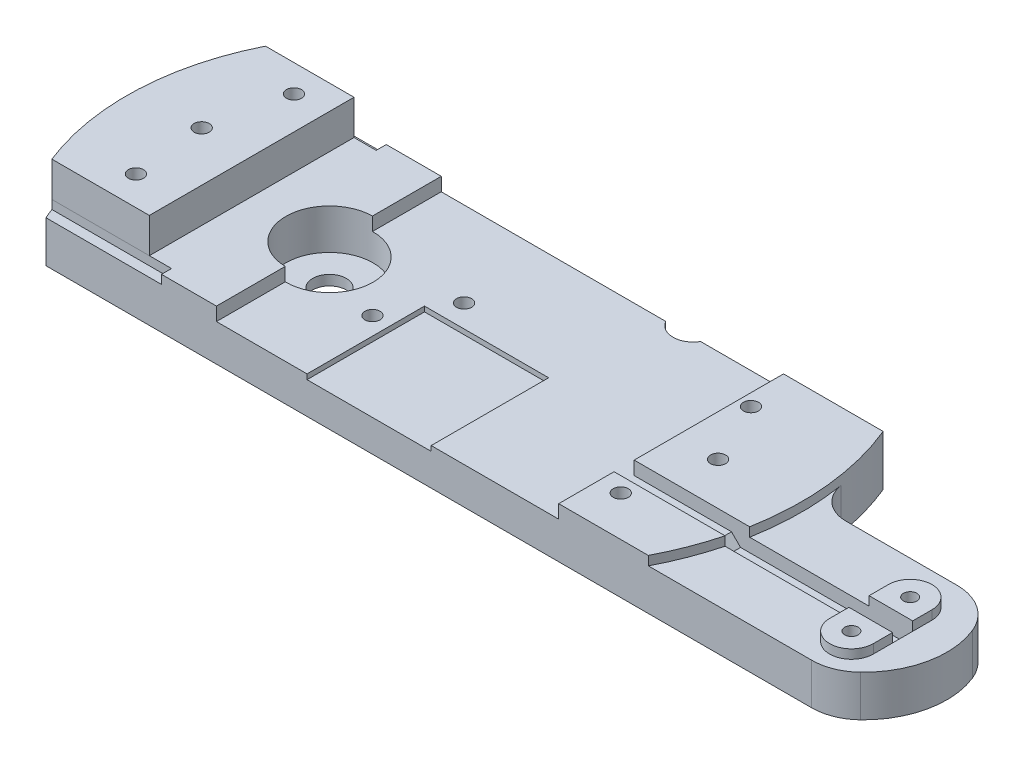
SolidWorks part; units mm, degrees
material "1060 Alloy"
ref_plane "Front Plane" through (0, 0, 0) normal (0, 0, 1) x (1, 0, 0)
ref_plane "Top Plane" through (0, 0, 0) normal (0, 1, 0) x (1, 0, 0)
ref_plane "Right Plane" through (0, 0, 0) normal (1, 0, 0) x (0, 0, -1)
sketch "Sketch1" plane through (0, 0, 0) normal (0, 1, 0) x (1, 0, 0)
  line L1 (-97.5, -33.5) -> (97.5, -33.5)
  line L2 (-97.5, -33.5) -> (-97.5, 33.5)
  line L3 (-97.5, 33.5) -> (97.5, 33.5)
  line L4 (97.5, -33.5) -> (97.5, 33.5)
  line L5 (-97.5, -33.5) -> (97.5, 33.5) construction
  line L6 (-97.5, 33.5) -> (97.5, -33.5) construction
  point P0 (0, 0)
  dimension "D1" = 67
  dimension "D2" = 195
extrude "Boss-Extrude1" add sketch "Sketch1" along normal blind 25.4
sketch "Sketch2" plane through (0, 0, 0) normal (0, -1, 0) x (1, 0, 0)
  line L0 (-97.5, -33.5) -> (-97.5, 33.5) construction
  line L1 (97.5, 33.5) -> (97.5, -33.5) construction
  line L2 (97.5, 33.5) -> (88.5, 33.5)
  line L3 (-97.5, 33.5) -> (97.5, 33.5) construction
  line L4 (97.5, -33.5) -> (91.5, -33.5)
  line L5 (97.5, -33.5) -> (-97.5, -33.5) construction
  line L6 (-97.5, 33.5) -> (-91, 33.5)
  line L7 (-97.5, -33.5) -> (-88, -33.5)
  circle A0 centre (18.0922, -3.2198) radius 79.4078
  circle A1 centre (-22.6589, 2.9929) radius 74.8411
  line M7 (97.5, -33.5) -> (97.5, 33.5)
  line M8 (97.5, 33.5) -> (-97.5, 33.5)
  line M9 (-97.5, 33.5) -> (-97.5, -33.5)
  line M10 (-97.5, -33.5) -> (97.5, -33.5)
  dimension "D1" = 9
  dimension "D2" = 6
  dimension "D3" = 6.5
  dimension "D4" = 9.5
extrude "Cut-Extrude1" cut sketch "Sketch2" against normal through all contours A0 M7 M8 | A0 M10 M7 | A1 M9 M10 | A1 M8 M9 region at (94.8284, 0, 24.4273) region at (95.7123, 0, -25.9883) region at (-95.5654, 0, 25.941) region at (-94.6839, 0, -24.4966)
sketch "Sketch3" plane through (0, 0, 33.5) normal (0, 0, -1) x (-1, 0, 0)
  line L0 (97.5, 25.4) -> (63.2, 25.4)
  line L2 (63.2, 25.4) -> (63.2, 15)
  line L3 (63.2, 15) -> (40.2, 15)
  line L4 (40.2, 15) -> (40.2, 11)
  line L5 (40.2, 11) -> (-61.8, 11)
  line L6 (-91.5, 25.4) -> (88, 25.4) construction
  line L10 (97.5, 0) -> (97.5, 25.4) construction
  line L11 (-61.8, 11) -> (-61.8, 15)
  line L12 (-61.8, 15) -> (-97.5, 15)
  line L13 (-97.5, 25.4) -> (-97.5, 0) construction
  line L14 (-97.5, 15) -> (-97.5, 25.4)
  line L15 (-97.5, 25.4) -> (63.2, 25.4)
  line M13 (-88.5, 0) -> (-88.5, 25.4)
  line M14 (-88.5, 25.4) -> (91, 25.4)
  dimension "D1" = 10.4
  dimension "D2" = 34.3
  dimension "D3" = 23
  dimension "D4" = 4
  dimension "D5" = 102
extrude "Cut-Extrude2" cut sketch "Sketch3" along normal through all contours L11 L12 L2 L3 L4 L5 M13 M14 | L2 L3 L4 L5 L11 L12 L14 L15 region at (12.2699, 18.7206, 33.5)
sketch "Sketch4" plane through (0, 25.4, 0) normal (0, 1, 0) x (1, 0, 0)
  line L0 (-56.5873, 33.5) -> (-56.5873, 30.5)
  line L1 (-63.2, 33.5) -> (-88, 33.5) construction
  line L2 (-56.5873, 30.5) -> (-89.5873, 30.5)
  line L3 (-56.5873, -33.5) -> (-56.5873, -30.5)
  line L4 (-91, -33.5) -> (-63.2, -33.5) construction
  line L5 (-56.5873, -30.5) -> (-92.2617, -30.5)
  line L6 (-56.5873, 33.5) -> (-63.2, 33.5)
  line L7 (-56.5873, -33.5) -> (-63.2, -33.5)
  arc A0 (-88, 33.5) -> (-91, -33.5) centre (-22.6589, -2.9929) ccw construction
  line M5 (-91, -33.5) -> (-63.2, -33.5)
  line M6 (-63.2, -33.5) -> (-63.2, 33.5)
  line M7 (-63.2, 33.5) -> (-88, 33.5)
  arc M8 (-88, 33.5) -> (-91, -33.5) centre (-22.6589, -2.9929) ccw
  dimension "D1" = 3
  dimension "D2" = 3
  dimension "D3" = 33
extrude "Cut-Extrude3" cut sketch "Sketch4" against normal blind 13 contours L2 M6 M7 M8 | L0 L6 L2 M6 | L5 M6 M8 M5 | L7 L3 L5 M6 region at (-59.8937, 25.4, -32) region at (-76.0082, 25.4, -31.9845) region at (-77.4242, 25.4, 31.9889) region at (-59.8937, 25.4, 32)
sketch "Sketch6" plane through (0, 0, 0) normal (0, -1, 0) x (1, 0, 0)
  line L0 (-63.2, -33.5) -> (-97.5, -33.5)
  line L1 (91.5, -33.5) -> (-88, -33.5) construction
  line L2 (-63.2, -33.5) -> (-63.2, 33.5)
  line L3 (-91, 33.5) -> (88.5, 33.5) construction
  line L4 (-63.2, -9) -> (-28.1, -9) construction
  line L5 (-63.2, 8.7) -> (-18.5, 8.7) construction
  line L6 (-63.2, -8.2) -> (-8.1, -8.2) construction
  line L8 (91.5, -33.5) -> (-88, -33.5) construction
  line L9 (-97.5, -33.5) -> (-97.5, 33.5)
  line L10 (-97.5, 33.5) -> (-63.2, 33.5)
  circle A1 centre (-18.5, 8.7) radius 2.25
  circle A2 centre (74.1, -1.7) radius 2.25
  circle A3 centre (68.3, 21.5) radius 2.25
  circle A4 centre (65.4, -20.2) radius 2.25
  circle A5 centre (-8.1, -8.2) radius 2.25
  circle A6 centre (-75.9, 21.8) radius 2.25
  circle A7 centre (-78, 0.1) radius 2.25
  circle A8 centre (-73, -22.4) radius 2.25
  arc A10 (-91, 33.5) -> (-88, -33.5) centre (-22.6589, 2.9929) ccw construction
  dimension "D22" = 4.5
  dimension "D3" = 35.1
  dimension "D4" = 34.3
  dimension "D5" = 44.7
  dimension "D6" = 24.5
  dimension "D7" = 55.1
  dimension "D8" = 42.2
  dimension "D9" = 137.3
  dimension "D10" = 128.6
  dimension "D11" = 131.5
  dimension "D12" = 9.8
  dimension "D13" = 14.8
  dimension "D14" = 12.7
  dimension "D15" = 11.1
  dimension "D16" = 33.6
  dimension "D17" = 55.3
  dimension "D18" = 31.8
  dimension "D19" = 55
  dimension "D20" = 13.3
  dimension "D21" = 25.3
extrude "Cut-Extrude4" cut sketch "Sketch6" against normal through all contours A5 | A1 | A6 | A7 | A8 | A4 | A2 | A3 region at (-18.5, 0, 8.7) region at (74.1, 0, -1.7) region at (68.3, 0, 21.5) region at (65.4, 0, -20.2) region at (-8.1, 0, -8.2) region at (-75.9, 0, 21.8) region at (-78, 0, 0.1) region at (-73, 0, -22.4)
sketch "Sketch7" plane through (0, 11, 0) normal (0, 1, 0) x (1, 0, 0)
  line L1 (-13.2, 1.5) -> (23.8, 1.5)
  line L2 (-13.2, 1.5) -> (-13.2, -33.5)
  line L3 (-13.2, -33.5) -> (23.8, -33.5)
  line L4 (23.8, 1.5) -> (23.8, -33.5)
  line L8 (-63.2, 30.5) -> (-63.2, -30.5) construction
  line L9 (-63.2, 30.5) -> (-63.2, -30.5) construction
  line L10 (-40.2, -33.5) -> (61.8, -33.5) construction
  dimension "D1" = 50
  dimension "D2" = 87
  dimension "D3" = 35
extrude "Cut-Extrude5" cut sketch "Sketch7" against normal blind 1.5
sketch "Sketch8" plane through (0, 25.4, 0) normal (0, 1, 0) x (1, 0, 0)
  line L0 (-56.5873, -33.5) -> (-97.5, -33.5)
  line L1 (-97.5, -33.5) -> (-97.5, 33.5)
  line L3 (-97.5, 33.5) -> (31.9, 33.5)
  line L6 (31.9, 36.5) -> (31.9, 30.5)
  line L7 (31.9, 33.5) -> (37.0962, 33.5)
  line L10 (-56.5873, 33.5) -> (-88, 33.5) construction
  line L11 (-40.2, 33.5) -> (61.8, 33.5) construction
  circle A1 centre (31.9, 36.5) radius 6
  arc A2 (-89.5873, 30.5) -> (-92.2617, -30.5) centre (-22.6589, -2.9929) ccw construction
  dimension "D1" = 12
  dimension "D2" = 129.4
extrude "Cut-Extrude6" cut sketch "Sketch8" against normal blind 18.5 contours L6 A1 L7 | L3 A1 L6 region at (29.8648, 25.4, -32.2699) region at (33.9352, 25.4, -32.2699)
sketch "Sketch9" plane through (0, 0, 0) normal (0, -1, 0) x (1, 0, 0)
  line L0 (88.5, 33.5) -> (137.2004, 33.5)
  line L1 (139.5727, -7.5) -> (97.3846, -7.5)
  arc A0 (153.4738, 1.8643) -> (147.5429, 29.3643) centre (130.3054, 11.2571) ccw
  arc A1 (91.5, -33.5) -> (88.5, 33.5) centre (18.0922, -3.2198) ccw construction
  arc A2 (142.3827, -10.6321) -> (147.5429, 29.3643) centre (130.3054, 11.2571) ccw construction
  arc A3 (147.5429, 29.3643) -> (137.2004, 33.5) centre (137.2004, 18.5) ccw
  arc A4 (147.5429, 29.3643) -> (137.9704, 33.4802) centre (137.2004, 18.5) ccw construction
  arc A5 (139.5727, -7.5) -> (153.4738, 1.8643) centre (139.5727, 7.5) ccw
  circle A6 centre (112.8948, -27.5) radius 16 construction
  circle A7 centre (103.4238, 59.4942) radius 16 construction
  circle A8 centre (112.8948, -27.5) radius 20 construction
  arc A9 (97.3846, -7.5) -> (88.5, 33.5) centre (18.0922, -3.2198) ccw
  circle A10 centre (138.3, 5.25) radius 2
  circle A11 centre (138.3, 22.75) radius 2
  circle A12 centre (138.3, 22.75) radius 2 construction
  circle A13 centre (138.3, 5.25) radius 2 construction
  dimension "D1" = 4
extrude "Boss-Extrude2" add sketch "Sketch9" against normal offset from surface (12.3 mm away) 1.3 up to face at (-16.25, 11, 8.7) offset beyond the face yes
fillet "Fillet1" radius 10 1 edges at (97.3846, 6.15, -7.5)
sketch "Sketch10" plane through (0, 0, 0) normal (0, -1, 0) x (1, 0, 0)
  circle A0 centre (-40.0178, 0) radius 13
  dimension "D1" = 26
extrude "Cut-Extrude7" cut sketch "Sketch10" against normal up to surface (15 mm away) from offset 3 up to face at (-54.1437, 15, 0) offset against normal yes
sketch "Sketch13" plane through (0, 0, 0) normal (0, -1, 0) x (1, 0, 0)
  circle A0 centre (-40.0178, 0) radius 5
  dimension "D1" = 10
extrude "Cut-Extrude9" cut sketch "Sketch13" against normal through all
sketch "Sketch11" plane through (0, 12.3, 0) normal (0, 1, 0) x (1, 0, 0)
  line L0 (138.3, -5.25) -> (138.3, -22.75) construction
  line L1 (144.8, -5.25) -> (144.8, -22.75)
  line L2 (131.8, -5.25) -> (131.8, -22.75)
  line L3 (131.8, -11) -> (144.8, -11)
  line L4 (131.8, -17) -> (144.8, -17)
  line L5 (131.8, -14) -> (144.8, -14) construction
  arc A0 (144.8, -5.25) -> (131.8, -5.25) centre (138.3, -5.25) ccw
  arc A1 (131.8, -22.75) -> (144.8, -22.75) centre (138.3, -22.75) ccw
  point P4 (138.3, -14)
  circle M15 centre (138.3, -22.75) radius 2
  circle M16 centre (138.3, -5.25) radius 2
  dimension "D1" = 13
  dimension "D2" = 6
extrude "Boss-Extrude3" add sketch "Sketch11" along normal up to surface (2.7 mm away) contours L1 A0 L2 L3 M16 | L2 A1 L1 L4 M15 region at (144.6214, 12.3, 8.125) region at (144.6214, 12.3, 19.875) up to face at (70.55, 15, 21.5)
sketch "Sketch12" plane through (0, 0, 11) normal (0, 0, 1) x (1, 0, 0)
  line L0 (144.8, 15) -> (144.8, 8.3)
  line L1 (144.8, 8.3) -> (93.5, 8.3)
  line L3 (97.5, 12.3) -> (88.5, 12.3) construction
  line L4 (90.8, 11) -> (61.8, 11)
  line L5 (61.8, 11) -> (61.8, 15)
  line L6 (61.8, 15) -> (88.5, 15) construction
  line L7 (61.8, 15) -> (144.8, 15)
  line L10 (97.5, 12.3) -> (93.5, 12.3) construction
  line L12 (88.5, 12.3) -> (137.2004, 12.3) construction
  line L13 (93.5, 12.3) -> (93.5, 8.3) construction
  line L14 (61.8, 11) -> (61.8, 15) construction
  line L15 (23.8, 11) -> (61.8, 11) construction
  line L16 (93.5, 8.3) -> (90.8, 11)
  dimension "D1" = 45
extrude "Cut-Extrude8" cut sketch "Sketch12" along normal up to surface (6 mm away) up to face at (138.3, 13.65, 17)
split "Split1" bodies to split 116 resulting bodies 114 115 split by face at (-52.6367, 15, 0)
